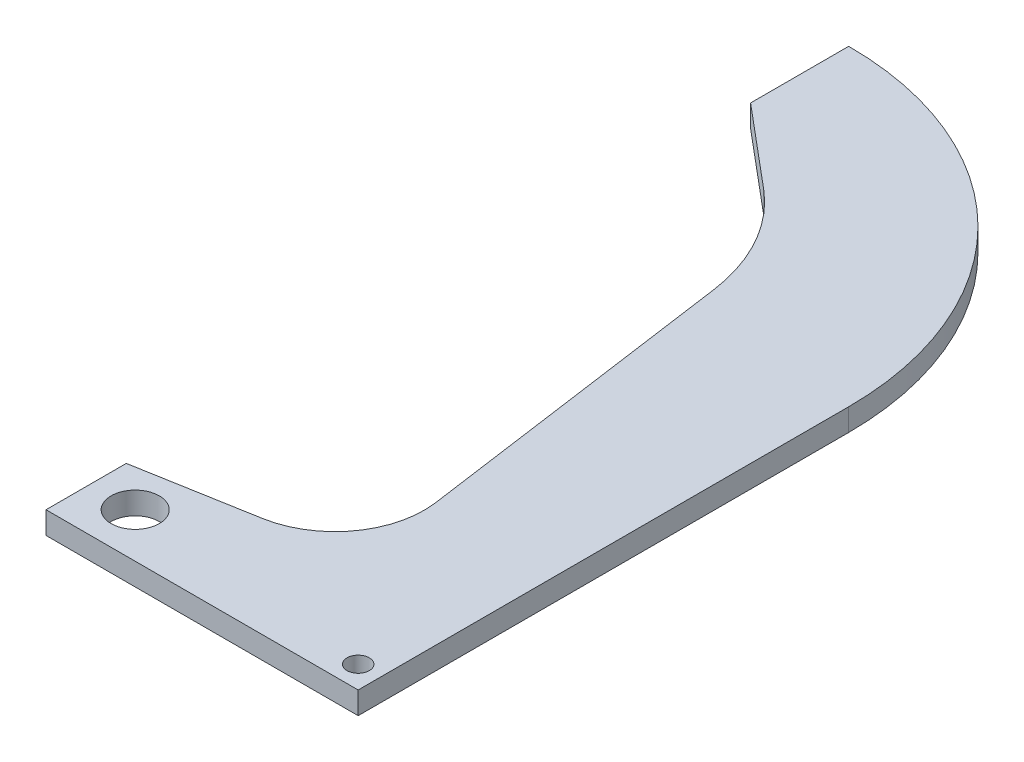
SolidWorks part; units mm, degrees
ref_plane "Front Plane" through (0, 0, 0) normal (0, 0, 1) x (1, 0, 0)
ref_plane "Top Plane" through (0, 0, 0) normal (0, 1, 0) x (1, 0, 0)
ref_plane "Right Plane" through (0, 0, 0) normal (1, 0, 0) x (0, 0, -1)
sketch "Sketch1" plane through (0, 0, 0) normal (0, 1, 0) x (1, 0, 0)
  line L1 (0, 0) -> (44.45, 0)
  line L2 (0, 0) -> (0, 114.3)
  line L4 (44.45, 0) -> (44.45, 69.85)
  circle A0 centre (6.35, 6.35) radius 3.429
  circle A1 centre (41.275, 3.175) radius 1.5875
  arc A2 (44.45, 69.85) -> (0, 114.3) centre (0, 69.85) ccw
  point P1 (44.45, 69.85)
  dimension "D3" = 6.858
  dimension "D6" = 3.175
  dimension "D1" = 44.45
  dimension "D4" = 6.35
  dimension "D5" = 6.35
  dimension "D7" = 3.175
  dimension "D8" = 3.175
  dimension "D2" = 114.3
extrude "Boss-Extrude1" add sketch "Sketch1" along normal blind 3.175
sketch "Sketch2" plane through (0, 3.175, 0) normal (0, 1, 0) x (1, 0, 0)
  line L1 (0, 114.3) -> (0, 0) construction
  line L2 (16.4996, 14.3393) -> (0, 11.43)
  line L3 (0, 11.43) -> (0, 100.33)
  line L4 (26.871, 28.6113) -> (20.4054, 74.6866)
  line L5 (11.5786, 90.6144) -> (0, 100.33)
  arc A0 (20.4054, 74.6866) -> (11.5786, 90.6144) centre (-4.7482, 71.1568) ccw
  arc A1 (26.871, 28.6113) -> (16.4996, 14.3393) centre (14.2943, 26.8464) cw
  point P11 (19.05, 84.3452)
  point P14 (28.575, 16.4685)
  dimension "D7" = 25.4
  dimension "D8" = 12.7
  dimension "D1" = 88.9
  dimension "D2" = 11.43
  dimension "D3" = 50
  dimension "D4" = 80
  dimension "D5" = 19.05
  dimension "D6" = 28.575
extrude "Cut-Extrude1" cut sketch "Sketch2" against normal through all
equation "\"tightTol\" = 0.005in"
equation "\"normTol\"= 0.01in"
equation "\"looseTol\"= 0.02in"
equation "\"D3@Sketch1\"=\"looseTol\"+0.25"
